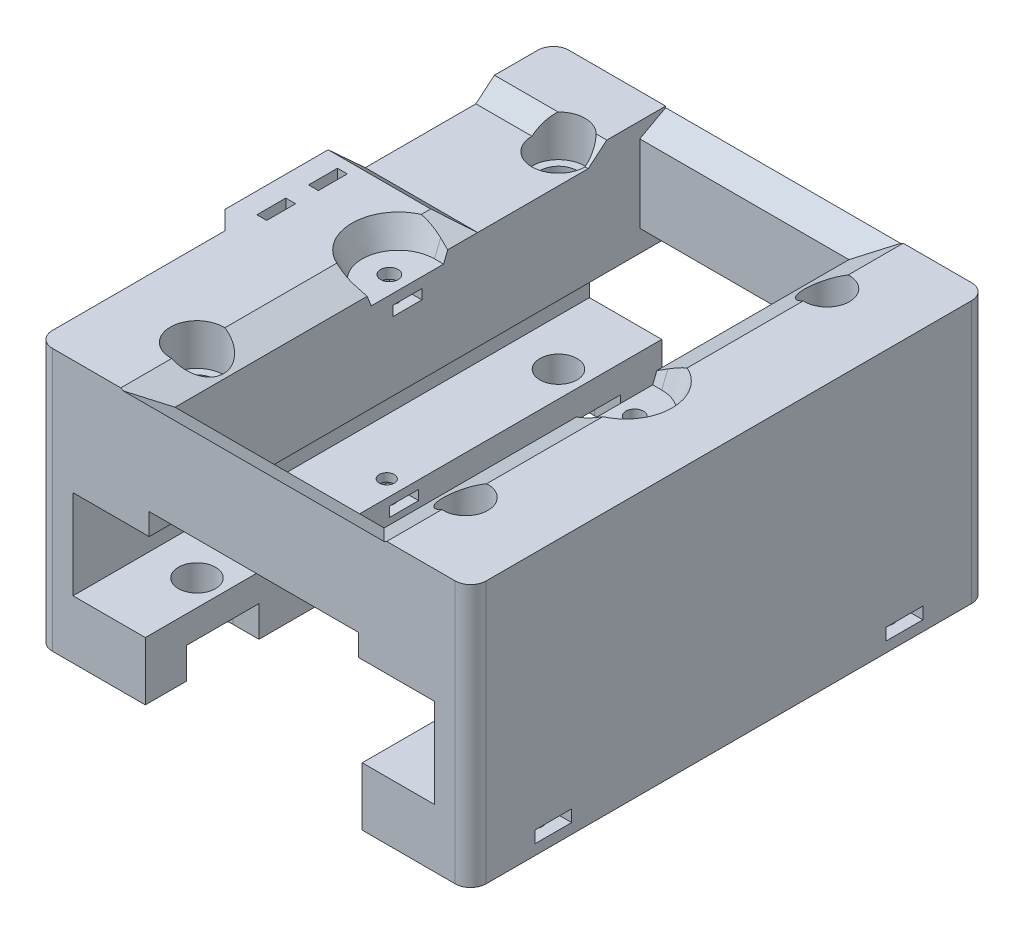
SolidWorks part; units mm, degrees
material "ABS"
ref_plane "Спереди" through (0, 0, 0) normal (0, 0, 1) x (1, 0, 0)
ref_plane "Сверху" through (0, 0, 0) normal (0, 1, 0) x (1, 0, 0)
ref_plane "Справа" through (0, 0, 0) normal (1, 0, 0) x (0, 0, -1)
sketch "Эскиз1" plane through (0, 0, 0) normal (0, 1, 0) x (1, 0, 0)
  line L1 (42, -50) -> (-42, -50)
  line L2 (42, -50) -> (42, 50)
  line L3 (42, 50) -> (-42, 50)
  line L4 (-42, -50) -> (-42, 50)
  line L5 (42, -50) -> (-42, 50) construction
  line L6 (42, 50) -> (-42, -50) construction
  point P0 (0, 0)
  dimension "D1" = 100
  dimension "D2" = 84
extrude "Бобышка-Вытянуть1" add sketch "Эскиз1" along normal blind 18
sketch "Эскиз2" plane through (0, 0, 50) normal (0, 0, 1) x (1, 0, 0)
  line L0 (0, 18) -> (0, -8) construction
  line L1 (-42, 0) -> (-19, 0)
  line L2 (-42, 0) -> (-42, -32.8)
  line L3 (-42, -32.8) -> (-19, -32.8)
  line L4 (-19, 0) -> (-19, -32.8)
  line L5 (-42, 18) -> (42, 18) construction
  line L6 (19, 0) -> (19, -32.8)
  line L7 (42, -32.8) -> (19, -32.8)
  line L8 (42, 0) -> (42, -32.8)
  line L9 (42, 0) -> (19, 0)
  dimension "D1" = 32.8
  dimension "D2" = 23
  dimension "D3" = 26
  dimension "D4" = 23
extrude "Бобышка-Вытянуть2" add sketch "Эскиз2" against normal up to surface (100 mm away) up to face at (0, 9, -50)
sketch "Эскиз5" plane through (0, 0, 50) normal (0, 0, 1) x (1, 0, 0)
  line L0 (0, -55) -> (0, 55) construction
  line L5 (19, -32.8) -> (42, -32.8) construction
  line L6 (-20.5, -21.5) -> (-35, -21.5)
  line L8 (-20.25, -4.2) -> (-35, -4.2)
  line L9 (-35, -21.5) -> (-35, -4.2)
  line L10 (-42, -32.8) -> (-19, -32.8) construction
  line L11 (-19, -32.8) -> (-20.5, -32.8)
  line L14 (-20.5, -32.8) -> (-20.5, -21.5)
  line L15 (20.5, -32.8) -> (20.5, -21.5)
  line L17 (19, -32.8) -> (20.5, -32.8)
  line L18 (35, -21.5) -> (35, -4.2)
  line L21 (20.5, -21.5) -> (35, -21.5)
  line L22 (20.25, -4.2) -> (35, -4.2)
  line L23 (-19, -4.2) -> (-19, -32.8)
  line L24 (19, -4.2) -> (19, -32.8)
  line L33 (-19, -4.2) -> (-19, 0)
  line L34 (-19, 0) -> (-20.25, 0)
  line L35 (-20.25, -4.2) -> (-20.25, 0)
  line L37 (19, -4.2) -> (19, 0)
  line L38 (19, 0) -> (20.25, 0)
  line L39 (20.25, -4.2) -> (20.25, 0)
  dimension "D1" = 17.3
  dimension "D2" = 16
  dimension "D3" = 11.3
  dimension "D4" = 17.3
  dimension "D5" = 1.5
  dimension "D6" = 1.5
  dimension "D7" = 11.3
  dimension "D8" = 1.25
  dimension "D9" = 1.25
extrude "Вырез-Вытянуть1" cut sketch "Эскиз5" against normal up to surface (100 mm away) up to face at (0, -11.9, -50)
hole_wizard "Отверстие1" positions "Эскиз8" profile "Эскиз10" legacy
sketch "Эскиз8" plane through (0, -32.8, 0) normal (0, -1, 0) x (-1, 0, 0)
  line L0 (-42, 50) -> (-20.5, 50) construction
  line L1 (-20.5, -50) -> (-42, -50) construction
  point P4 (-26, -35)
  point P6 (-26, 35)
  dimension "D1" = 15
  dimension "D2" = 15
  dimension "D4" = 26
  dimension "D8" = 26
sketch "Эскиз10" plane through (26, -32.8, 35) normal (1, 0, 0) x (0, 0, -1)
  line L0 (0, 0) -> (0, 45)
  line L1 (0, 45) -> (2.3, 45)
  line L2 (2.3, 45) -> (2.3, 6)
  line L3 (2.3, 6) -> (4.8, 6)
  line L4 (4.8, 6) -> (4.8, 0)
  line L5 (4.8, 0) -> (0, 0)
  line L10 (0, 45) -> (-2.3, 45) construction
  line L11 (0, -6.35) -> (0, 107.95) construction
  dimension "Диаметр отверстия" = 4.6
  dimension "Глубина отверстия" = 45
  dimension "Диаметр цековки" = 9.6
  dimension "Глубина цековки" = 6
  dimension "Угол заточки сверла" = 180
sketch "Эскиз12" plane through (0, 18, 0) normal (0, 1, 0) x (1, 0, 0)
  line L5 (-20.25, -45) -> (20.25, -45)
  line L6 (-20.25, -45) -> (-20.25, 45)
  line L7 (-20.25, 45) -> (20.25, 45)
  line L8 (20.25, -45) -> (20.25, 45)
  line L9 (-20.25, -45) -> (20.25, 45) construction
  line L10 (-20.25, 45) -> (20.25, -45) construction
  point P0 (0, 0)
  dimension "D1" = 90
  dimension "D2" = 40.5
extrude "Вырез-Вытянуть3" cut sketch "Эскиз12" against normal up to next
sketch "Эскиз13" plane through (0, 18, 0) normal (0, 1, 0) x (1, 0, 0)
  line L0 (22, 7) -> (-20.25, 7)
  line L1 (-20.25, 45) -> (-20.25, -45) construction
  line L2 (-20.25, 7) -> (-20.25, -7)
  line L3 (-20.25, -7) -> (22, -7)
  line L4 (0, -27.94) -> (0, 27.94) construction
  line L5 (20.25, -7) -> (-22, -7)
  line L6 (20.25, 7) -> (20.25, -7)
  line L7 (-22, 7) -> (20.25, 7)
  arc A0 (22, -7) -> (22, 7) centre (22, 0) ccw
  arc A1 (-22, -7) -> (-22, 7) centre (-22, 0) cw
  dimension "D1" = 14
  dimension "D2" = 22
extrude "Вырез-Вытянуть4" cut sketch "Эскиз13" against normal blind 5 flip side to cut
hole_wizard "Отверстие с зазором M31" positions "Эскиз14" profile "Эскиз15" hole size "M3" standard "ISO"
sketch "Эскиз14" plane through (0, 13, 0) normal (0, 1, 0) x (1, 0, 0)
  line L0 (-42, -50) -> (42, -50) construction
  point P0 (-23.75, 0)
  point P2 (23.75, 0)
  dimension "D1" = 23.75
  dimension "D2" = 23.75
  dimension "D3" = 50
  dimension "D4" = 50
sketch "Эскиз15" plane through (-23.75, 13, 0) normal (1, 0, 0) x (0, 0, 1)
  line L0 (0, 0) -> (0, 7.0215)
  line L1 (0, 7.0215) -> (1.7, 6)
  line L2 (1.7, 6) -> (1.7, 0)
  line L5 (1.7, 0) -> (0, 0)
  line L10 (0, 7.0215) -> (-1.7, 6) construction
  line L11 (0, -6.35) -> (0, 107.95) construction
  dimension "Диаметр отверстия" = 3.4
  dimension "Глубина отверстия" = 6
  dimension "Угол заточки сверла" = 118
sketch "Эскиз16" plane through (0, -32.8, 0) normal (0, -1, 0) x (1, 0, 0)
  line L2 (42, -50) -> (42, 50) construction
  circle A0 centre (37.82, 34) radius 2
  circle A1 centre (37.82, -34) radius 2
  dimension "D1" = 4
  dimension "D2" = 4
  dimension "D3" = 4.18
  dimension "D4" = 4.18
  dimension "D5" = 68
  dimension "D6" = 34
extrude "Вырез-Вытянуть6" cut sketch "Эскиз16" against normal blind 8
sketch "Эскиз17" plane through (42, 0, 0) normal (1, 0, 0) x (0, 0, -1)
  line L1 (-30.45, -30.8) -> (-37.55, -30.8)
  line L2 (-30.45, -30.8) -> (-30.45, -28.5)
  line L3 (-30.45, -28.5) -> (-37.55, -28.5)
  line L4 (-37.55, -30.8) -> (-37.55, -28.5)
  line L5 (50, -32.8) -> (-50, -32.8) construction
  line L6 (30.45, -30.8) -> (37.55, -30.8)
  line L7 (30.45, -30.8) -> (30.45, -28.5)
  line L8 (30.45, -28.5) -> (37.55, -28.5)
  line L9 (37.55, -30.8) -> (37.55, -28.5)
  line L11 (50, 18) -> (50, -32.8) construction
  line L12 (-50, 18) -> (-50, -32.8) construction
  dimension "D1" = 2.3
  dimension "D2" = 7.1
  dimension "D4" = 12.45
  dimension "D5" = 2.3
  dimension "D6" = 7.1
  dimension "D7" = 2
  dimension "D8" = 2
  dimension "D9" = 12.45
extrude "Вырез-Вытянуть7" cut sketch "Эскиз17" against normal blind 7.93
sketch "Эскиз18" plane through (-42, 0, 0) normal (-1, 0, 0) x (0, 0, 1)
  line L0 (-50, 18) -> (50, 18) construction
  line L1 (-10, 18) -> (10, 18)
  line L2 (-10, 18) -> (-10, 3)
  line L3 (-10, 3) -> (10, 3)
  line L4 (10, 18) -> (10, 3)
  line L6 (-50, 18) -> (-50, -32.8) construction
  point P8 (-10, 10.5)
  dimension "D1" = 15
  dimension "D2" = 20
  dimension "D3" = 40
extrude "Бобышка-Вытянуть3" add sketch "Эскиз18" along normal blind 3.6
sketch "Эскиз21" plane through (0, 18, 0) normal (0, 1, 0) x (1, 0, 0)
  line L0 (-42, 50) -> (-42, 10) construction
  line L1 (-20.25, 35) -> (-42, 35)
  line L2 (-20.25, 35) -> (-20.25, 13.6)
  line L3 (-20.25, 13.6) -> (-42, 13.6)
  line L4 (-42, 35) -> (-42, 13.6)
  line L5 (42, 50) -> (-42, 50) construction
  dimension "D1" = 21.4
  dimension "D2" = 15
extrude "Вырез-Вытянуть9" cut sketch "Эскиз21" against normal blind 3
fillet "Скругление3" radius 3 4 edges at (42, -7.4, 50) (42, -7.4, -50) (-42, -7.4, -50) (-42, -7.4, 50)
sketch "Эскиз23" plane through (0, 18, 0) normal (0, 1, 0) x (1, 0, 0)
  line L0 (-45.6, 10) -> (-42, 13.6)
  line L1 (-42, 35) -> (-42, 13.6) construction
  line L2 (-42, 13.6) -> (-42, 10)
  line L3 (-42, 10) -> (-45.6, 10)
  line L4 (-45.6, -10) -> (-42, -10)
  line L5 (-42, -10) -> (-42, -13.6)
  line L6 (-42, -10) -> (-42, -47) construction
  line L7 (-42, -13.6) -> (-45.6, -10)
  dimension "D1" = 45
  dimension "D2" = 45
  dimension "D3" = 3.6
extrude "Бобышка-Вытянуть5" add sketch "Эскиз23" against normal up to surface (15 mm away) up to face at (-43.8, 3, 0)
chamfer "Фаска1" distance 5 distance2 2 3 edges at (-21.125, 18, 7) (-21.125, 18, -7) (-29, 18, 0) first distance on face at (-21.125, 15.5, 7) first distance on face at (-21.125, 15.5, -7) first distance on face at (-25.5, 15.5, 0)
chamfer "Фаска2" distance 2 distance2 5 3 edges at (21.125, 18, 7) (21.125, 18, -7) (29, 18, 0) first distance on face at (-9.6185, 18, -3.0963)
chamfer "Фаска4" distance 5.5 distance2 3 6 edges at (-20.25, 18, 27) (0, 18, 45) (20.25, 18, 27) (20.25, 18, -27) (0, 18, -45) (-20.25, 18, -11.3) first distance on face at (-9.5444, 18, -3.0963)
sketch "Эскиз25" plane through (0, -4.2, 0) normal (0, -1, 0) x (1, 0, 0)
  line L0 (39, -50) -> (25.75, -50) construction
  line L1 (25.75, 50) -> (39, 50) construction
  circle A0 centre (-26, 35) radius 3.6
  circle A1 centre (-26, -35) radius 3.6
  circle A4 centre (26, -35) radius 2.3 construction
  circle A5 centre (26, 35) radius 2.3 construction
  dimension "D3" = 7.2
  dimension "D4" = 7.2
  dimension "D1" = 52
  dimension "D2" = 52
  dimension "D5" = 15
  dimension "D6" = 15
extrude "Вырез-Вытянуть11" cut sketch "Эскиз25" against normal blind 2.6
sketch "Эскиз26" plane through (0, 18, 0) normal (0, 1, 0) x (1, 0, 0)
  circle A0 centre (-26, -35) radius 5.15
  circle A1 centre (-26, 35) radius 5.15
  dimension "D1" = 10.3
  dimension "D2" = 10.3
extrude "Вырез-Вытянуть12" cut sketch "Эскиз26" against normal blind 8
sketch "Эскиз27" plane through (0, -32.8, 0) normal (0, -1, 0) x (1, 0, 0)
  circle A4 centre (-26, 35) radius 3.6
  circle A5 centre (-26, -35) radius 3.6
  dimension "D1" = 7.2
  dimension "D2" = 7.2
extrude "Вырез-Вытянуть13" cut sketch "Эскиз27" against normal up to next
sketch "Эскиз28" plane through (0, -32.8, 0) normal (0, -1, 0) x (1, 0, 0)
  line L0 (-26, -28) -> (-20.5, -28)
  line L1 (-20.5, -50) -> (-20.5, 50) construction
  line L2 (-20.5, -28) -> (-20.5, -42)
  line L3 (-20.5, -42) -> (-26, -42)
  line L4 (-26, 42) -> (-20.5, 42)
  line L7 (-20.5, 28) -> (-26, 28)
  line L8 (-20.5, 42) -> (-20.5, 28)
  arc A2 (-26, 42) -> (-26, 28) centre (-26, 35) ccw
  arc A3 (-26, -28) -> (-26, -42) centre (-26, -35) ccw
  dimension "D1" = 14
  dimension "D2" = 14
extrude "Вырез-Вытянуть14" cut sketch "Эскиз28" against normal blind 6
sketch "Эскиз30" plane through (0, 18, 0) normal (0, 1, 0) x (1, 0, 0)
  circle A0 centre (26, -35) radius 4.35
  circle A1 centre (26, 35) radius 4.35
extrude "Вырез-Вытянуть16" cut sketch "Эскиз30" against normal blind 8
sketch "Эскиз31" plane through (0, -32.8, 0) normal (0, -1, 0) x (1, 0, 0)
  line L0 (-20.5, -50) -> (-39, -50) construction
  line L1 (-20.5, 50) -> (-21, 50)
  line L2 (-20.5, 50) -> (-20.5, -50)
  line L3 (-20.5, -50) -> (-21, -50)
  line L4 (-21, 50) -> (-21, -50)
  line L5 (39, -50) -> (20.5, -50) construction
  line L6 (20.5, 50) -> (21, 50)
  line L7 (20.5, 50) -> (20.5, -50)
  line L8 (20.5, -50) -> (21, -50)
  line L9 (21, 50) -> (21, -50)
  dimension "D1" = 0.5
  dimension "D2" = 0.5
extrude "Вырез-Вытянуть17" cut sketch "Эскиз31" against normal up to surface (11.3 mm away) up to face at (-22.4, -21.5, 35)
sketch "Эскиз32" plane through (0, -1.6, 0) normal (0, -1, 0) x (1, 0, 0)
  circle A0 centre (-26, 35) radius 3.6
  circle A3 centre (-26, -35) radius 3.6
  dimension "D1" = 7.2
  dimension "D2" = 7.2
extrude "Вырез-Вытянуть18" cut sketch "Эскиз32" against normal up to next
sketch "Эскиз33" plane through (0, -32.8, 0) normal (0, -1, 0) x (1, 0, 0)
  line L2 (23.8, 39.2661) -> (28.2, 39.2661)
  line L11 (23.4054, 30.9617) -> (21.2054, 34.7722)
  line L18 (23.8, 30.7339) -> (28.2, 30.7339)
  line L19 (21.2054, 35.2278) -> (23.4054, 39.0383)
  line L20 (28.5946, 30.9617) -> (30.7946, 34.7722)
  line L21 (30.7946, 35.2278) -> (28.5946, 39.0383)
  line L22 (27.94, 0) -> (-27.94, 0) construction
  line L23 (30.7946, -35.2278) -> (28.5946, -39.0383)
  line L24 (28.5946, -30.9617) -> (30.7946, -34.7722)
  line L25 (21.2054, -35.2278) -> (23.4054, -39.0383)
  line L26 (23.8, -30.7339) -> (28.2, -30.7339)
  line L27 (23.4054, -30.9617) -> (21.2054, -34.7722)
  line L28 (23.8, -39.2661) -> (28.2, -39.2661)
  arc A5 (30.7946, -35.2278) -> (28.5946, -39.0383) centre (26, -35) cw
  arc A6 (23.4054, 39.0383) -> (21.2054, 35.2278) centre (26, 35) ccw
  arc A25 (28.2, 39.2661) -> (23.8, 39.2661) centre (26, 35) ccw
  arc A26 (21.2054, 34.7722) -> (23.4054, 30.9617) centre (26, 35) ccw
  arc A27 (23.8, 30.7339) -> (28.2, 30.7339) centre (26, 35) ccw
  arc A28 (28.5946, 30.9617) -> (30.7946, 34.7722) centre (26, 35) ccw
  arc A29 (30.7946, 35.2278) -> (28.5946, 39.0383) centre (26, 35) ccw
  arc A30 (28.2, -39.2661) -> (23.8, -39.2661) centre (26, -35) cw
  arc A31 (23.4054, -39.0383) -> (21.2054, -35.2278) centre (26, -35) cw
  arc A32 (21.2054, -34.7722) -> (23.4054, -30.9617) centre (26, -35) cw
  arc A33 (23.8, -30.7339) -> (28.2, -30.7339) centre (26, -35) cw
  arc A34 (28.5946, -30.9617) -> (30.7946, -34.7722) centre (26, -35) cw
  dimension "D1" = 4.4
  dimension "D6" = 4.4
  dimension "D7" = 120
  dimension "D2" = 9.6
  dimension "D3" = 4.4
  dimension "D4" = 120
  dimension "D5" = 4.4
  dimension "D8" = 120
  dimension "D9" = 4.4
  dimension "D10" = 120
  dimension "D11" = 4.4
  dimension "D12" = 120
extrude "Бобышка-Вытянуть6" add sketch "Эскиз33" against normal up to surface (6 mm away) up to face at (26, -26.8, -37.3)
sketch "Эскиз34" plane through (0, -32.8, 0) normal (0, -1, 0) x (1, 0, 0)
  line L11 (-35, 12) -> (-35, 18)
  line L30 (21, -12) -> (-21, -12)
  line L31 (35, -12) -> (35, 12)
  line L34 (20.3903, 12) -> (-21, 12)
  line L45 (-35, -12) -> (-35, 12)
  line L46 (35, -12) -> (-35, 12) construction
  line L47 (35, 12) -> (-35, -12) construction
  line L49 (27.94, 0) -> (-27.94, 0) construction
  line L51 (-35, -12) -> (-35, -18)
  line L52 (0, -27.94) -> (0, 27.94) construction
  line L53 (35, -12) -> (35, -18)
  line L55 (35, 12) -> (35, 18)
  line L58 (-21, 28) -> (-21, -28) construction
  line L60 (21, -50) -> (21, 50) construction
  line L61 (-35, 18) -> (-21, 12)
  line L62 (-35, -18) -> (-21, -12)
  line L63 (20.3903, 12) -> (35, 18)
  line L64 (21, -12) -> (35, -18)
  point P0 (0, 0)
  point P12 (-35, 15)
  point P17 (35, 15)
  dimension "D1" = 24
  dimension "D2" = 70
  dimension "D3" = 6
  dimension "D4" = 24
extrude "Вырез-Вытянуть19" cut sketch "Эскиз34" against normal blind 6
sketch "Эскиз35" plane through (0, -32.8, 0) normal (0, -1, 0) x (1, 0, 0)
  line L0 (27.94, 0) -> (-27.94, 0) construction
  line L1 (0, -27.94) -> (0, 27.94) construction
  circle A4 centre (-34.4682, 17.1531) radius 1
  circle A5 centre (-34.4682, -17.1531) radius 1
  circle A6 centre (34.4682, 17.1531) radius 1
  circle A7 centre (34.4682, -17.1531) radius 1
extrude "Вырез-Вытянуть20" cut sketch "Эскиз35" against normal blind 6
fillet "Скругление4" radius 10 8 edges at (35, -29.8, -16.3062) (33.4882, -29.8, -17.3521) (33.4947, -29.8, 17.3818) (35, -29.8, 16.3062) (-33.4882, -29.8, -17.3521) (-35, -29.8, -16.3062) (-33.4882, -29.8, 17.3521) (-35, -29.8, 16.3062)
fillet "Скругление5" radius 1 4 edges at (-21, -29.8, 12) (-21, -29.8, -12) (21, -29.8, -12) (21, -29.8, 12.2504)
sketch "Эскиз36" plane through (-21, 0, 0) normal (1, 0, 0) x (0, 0, -1)
  line L0 (47, -32.8) -> (-47, -32.8) construction
  line L5 (2.9271, -25) -> (-2.6729, -25)
  line L6 (2.9271, -25) -> (2.9271, -23.1)
  line L7 (2.9271, -23.1) -> (-2.6729, -23.1)
  line L8 (-2.6729, -25) -> (-2.6729, -23.1)
  line L9 (2.9271, -25) -> (-2.6729, -23.1) construction
  line L10 (2.9271, -23.1) -> (-2.6729, -25) construction
  point P0 (0.1271, -24.05)
  dimension "D1" = 1.9
  dimension "D2" = 5.6
  dimension "D3" = 7.8
extrude "Вырез-Вытянуть21" cut sketch "Эскиз36" against normal blind 6
hole_wizard "Отверстие с зазором M2.52" positions "Эскиз37" profile "Эскиз38" hole size "M2.5" standard "ISO"
sketch "Эскиз37" plane through (0, -26.8, 0) normal (0, -1, 0) x (-1, 0, 0)
  line L0 (21, 13.5165) -> (21, -13.5165) construction
  line L1 (-21, -13.7421) -> (-21, 13.5165) construction
  point P0 (24.25, 0)
  point P2 (-24.25, 0)
  dimension "D1" = 3.25
  dimension "D2" = 3.25
sketch "Эскиз38" plane through (-24.25, -26.8, 0) normal (1, 0, 0) x (0, 0, -1)
  line L0 (0, 0) -> (0, 6.1712)
  line L1 (0, 6.1712) -> (1.45, 5.3)
  line L2 (1.45, 5.3) -> (1.45, 0)
  line L5 (1.45, 0) -> (0, 0)
  line L10 (0, 6.1712) -> (-1.45, 5.3) construction
  line L11 (0, -6.35) -> (0, 107.95) construction
  dimension "Диаметр отверстия" = 2.9
  dimension "Глубина отверстия" = 5.3
  dimension "Угол заточки сверла" = 118
mirror "Зеркальное отражение1" about plane through (0, 0, 0) normal (1, 0, 0) of "Вырез-Вытянуть21"
sketch "Эскиз39" plane through (0, -32.8, 0) normal (0, -1, 0) x (1, 0, 0)
  line L0 (21, 13.7421) -> (21, 50) construction
  line L5 (22, 36.6041) -> (21, 36.6041)
  line L6 (22, 33.3959) -> (22, 36.6041)
  line L7 (23.4054, 30.9617) -> (21.2054, 34.7722) construction
  line L8 (21.2054, 35.2278) -> (23.4054, 39.0383) construction
  line L9 (21, 36.6041) -> (21, 33.3959)
  line L10 (21, 33.3959) -> (22, 33.3959)
  line L11 (27.94, 0) -> (-27.94, 0) construction
  line L12 (21, -33.3959) -> (22, -33.3959)
  line L13 (21, -36.6041) -> (21, -33.3959)
  line L14 (22, -33.3959) -> (22, -36.6041)
  line L15 (22, -36.6041) -> (21, -36.6041)
  dimension "D1" = 1
extrude "Вырез-Вытянуть22" cut sketch "Эскиз39" against normal up to surface (6 mm away) up to face at (26, -26.8, -37.3)
fillet "Скругление6" radius 0.5 8 edges at (21, -29.8, 36.6041) (22, -29.8, 36.6041) (21, -29.8, 33.3959) (22, -29.8, 33.3959) (21, -29.8, -36.6041) (22, -29.8, -36.6041) (21, -29.8, -33.3959) (22, -29.8, -33.3959)
sketch "Эскиз41" plane through (20.25, 0, 0) normal (-1, 0, 0) x (0, 0, 1)
  line L0 (7, 13) -> (-7, 13) construction
  line L1 (-2.8, 11) -> (2.8, 11)
  line L2 (-2.8, 11) -> (-2.8, 9.1)
  line L3 (-2.8, 9.1) -> (2.8, 9.1)
  line L4 (2.8, 11) -> (2.8, 9.1)
  dimension "D1" = 5.6
  dimension "D2" = 1.9
  dimension "D3" = 2
  dimension "D4" = 2.8
extrude "Вырез-Вытянуть23" cut sketch "Эскиз41" against normal blind 6.3
mirror "Зеркальное отражение2" about plane through (0, 0, 0) normal (1, 0, 0) of "Вырез-Вытянуть23"
chamfer "Фаска5" distance 3.6 distance2 3 3 edges at (-20.55, 18, -35) (-36.575, 18, -35) (-33.875, 18, -13.6) first distance on face at (-30.8745, 18, -41.8245) first distance on face at (-35.1643, 18, 17.0018)
sketch "Эскиз42" plane through (0, 18, 0) normal (0, 1, 0) x (1, 0, 0)
  line L0 (-25.75, 10) -> (-45.6, 10) construction
  line L1 (-41.6, 7.8) -> (-39.7, 7.8)
  line L2 (-41.6, 7.8) -> (-41.6, 2.2)
  line L3 (-41.6, 2.2) -> (-39.7, 2.2)
  line L4 (-39.7, 7.8) -> (-39.7, 2.2)
  line L5 (-41.6, -2.2) -> (-39.7, -2.2)
  line L6 (-41.6, -2.2) -> (-41.6, -7.8)
  line L7 (-41.6, -7.8) -> (-39.7, -7.8)
  line L8 (-39.7, -2.2) -> (-39.7, -7.8)
  line L9 (-45.6, -10) -> (-45.6, 10) construction
  dimension "D1" = 1.9
  dimension "D2" = 5.6
  dimension "D3" = 5.6
  dimension "D4" = 1.9
  dimension "D5" = 10
  dimension "D6" = 2.2
  dimension "D7" = 4
  dimension "D8" = 4
extrude "Вырез-Вытянуть24" cut sketch "Эскиз42" against normal blind 7.75
sketch "Эскиз43" plane through (-45.6, 0, 0) normal (-1, 0, 0) x (0, 0, 1)
  line L0 (-10, 18) -> (-10, 3) construction
  line L1 (10, 18) -> (-10, 18) construction
  circle A0 centre (-5, 13) radius 1.55
  circle A1 centre (5, 13) radius 1.55
  dimension "D1" = 3.1
  dimension "D2" = 3.1
  dimension "D3" = 10
  dimension "D4" = 5
  dimension "D5" = 5
extrude "Вырез-Вытянуть25" cut sketch "Эскиз43" against normal blind 10
